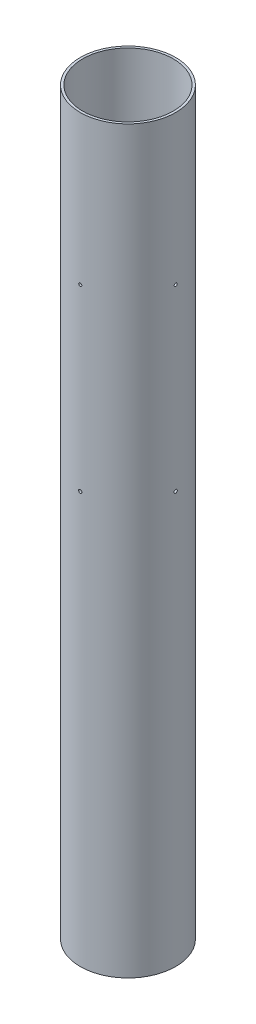
SolidWorks part; units mm, degrees
material "E-Glass Fiber"
ref_plane "Front Plane" through (0, 0, 0) normal (0, 0, 1) x (1, 0, 0)
ref_plane "Top Plane" through (0, 0, 0) normal (0, 1, 0) x (1, 0, 0)
ref_plane "Right Plane" through (0, 0, 0) normal (1, 0, 0) x (0, 0, -1)
sketch "Sketch1" plane through (0, 0, 0) normal (0, 1, 0) x (1, 0, 0)
  circle A0 centre (0, 0) radius 50.8
  dimension "D1" = 101.6
extrude "Coupler Extrusion" add sketch "Sketch1" along normal blind 787.4 thin thin type one direction reverse wall 2.54
ref_plane "Plane1" through (0, 0, 50.8) normal (0, 0, 1) x (1, 0, 0)
sketch "Sketch2" plane through (0, 0, 50.8) normal (0, 0, 1) x (1, 0, 0)
  line L0 (0, 787.4) -> (0, 0) construction
  line L1 (48.26, 787.4) -> (-48.26, 787.4) construction
  circle A0 centre (0, 628.65) radius 1.6383
  dimension "D1" = 3.2766
  dimension "D2" = 158.75
extrude "Bulkhead Hole" cut sketch "Sketch2" against normal up to next
pattern_circular "CirPattern1" count 4 over 360 about axis through (0, 787.4, 0) along (0, -1, 0) of "Bulkhead Hole"
sketch "Sketch3" plane through (0, 0, 50.8) normal (0, 0, 1) x (1, 0, 0)
  line L0 (0, 787.4) -> (0, 0) construction
  line L1 (50.8, 787.4) -> (-50.8, 787.4) construction
  line L2 (-48.26, 0) -> (48.26, 0) construction
  line L3 (-50.8, 0) -> (50.8, 0) construction
  line L4 (48.26, 787.4) -> (-48.26, 787.4) construction
  circle A0 centre (0, 438.15) radius 1.7526
  dimension "D1" = 3.5052
  dimension "D2" = 438.15
  dimension "D3" = 349.25
extrude "Lower Bulkhead Hole" cut sketch "Sketch3" against normal up to next
pattern_circular "CirPattern2" count 4 over 360 about axis through (0, 787.4, 0) along (0, -1, 0) of "Lower Bulkhead Hole" reverse direction yes
